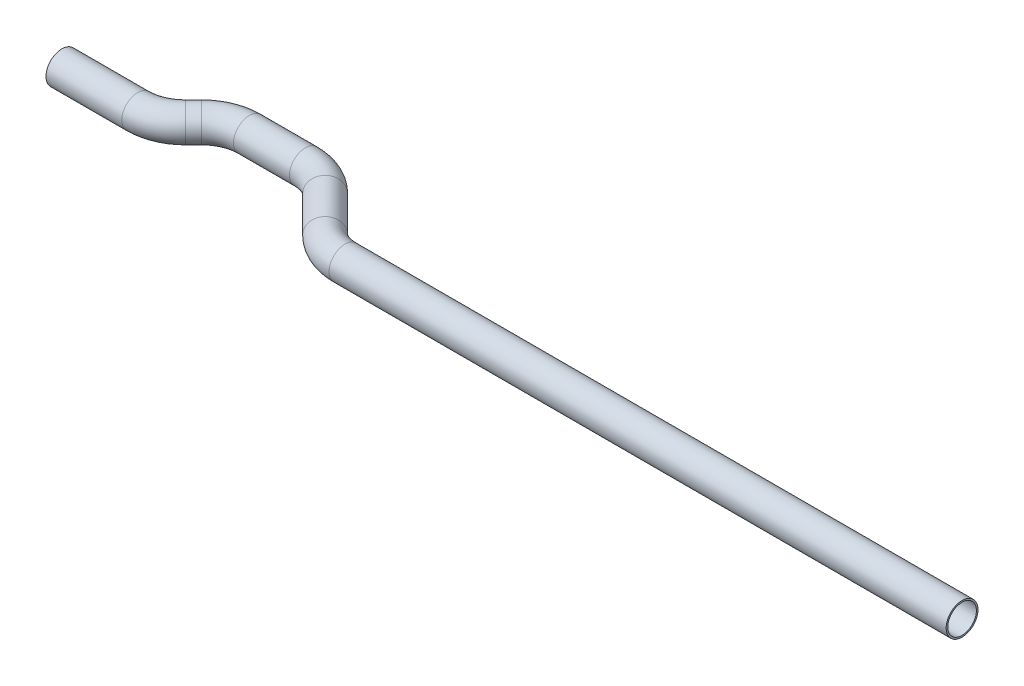
SolidWorks part; units mm, degrees
ref_plane "Front Plane" through (0, 0, 0) normal (0, 0, 1) x (1, 0, 0)
ref_plane "Top Plane" through (0, 0, 0) normal (0, 1, 0) x (1, 0, 0)
ref_plane "Right Plane" through (0, 0, 0) normal (1, 0, 0) x (0, 0, -1)
sketch "Sketch1" plane through (0, 0, 0) normal (0, 1, 0) x (1, 0, 0)
  line L0 (0, 0) -> (30.2092, 0)
  line L1 (43.6796, 5.5796) -> (46.9142, 8.8142)
  line L2 (60.3846, 14.3939) -> (82.7031, 14.3939)
  line L3 (96.1735, 8.8142) -> (110.4142, -5.4265)
  line L4 (123.8846, -11.0061) -> (369.9939, -11.0061)
  arc A0 (110.4142, -5.4265) -> (123.8846, -11.0061) centre (123.8846, 8.0439) ccw
  arc A1 (82.7031, 14.3939) -> (96.1735, 8.8142) centre (82.7031, -4.6561) cw
  arc A2 (46.9142, 8.8142) -> (60.3846, 14.3939) centre (60.3846, -4.6561) cw
  arc A3 (30.2092, 0) -> (43.6796, 5.5796) centre (30.2092, 19.05) ccw
  point P8 (115.9939, -11.0061)
  point P11 (90.5939, 14.3939)
  point P15 (52.4939, 14.3939)
  point P18 (38.1, 0)
  dimension "D6" = 14.3939
  dimension "D8" = 19.05
  dimension "D1" = 38.1
  dimension "D2" = 38.1
  dimension "D3" = 254
  dimension "D4" = 45
  dimension "D5" = 45
  dimension "D7" = 25.4
ref_plane "Plane1" through (0, 0, 0) normal (1, 0, 0) x (0, 0, -1)
sketch "Sketch2" plane through (0, 0, 0) normal (1, 0, 0) x (0, 0, -1)
  circle A0 centre (0, 0) radius 6.35
  circle A1 centre (0, 0) radius 5.715
  dimension "D1" = 12.7
  dimension "D2" = 0.635
sweep "Sweep1" add profiles "Sketch2" path "Sketch1"
